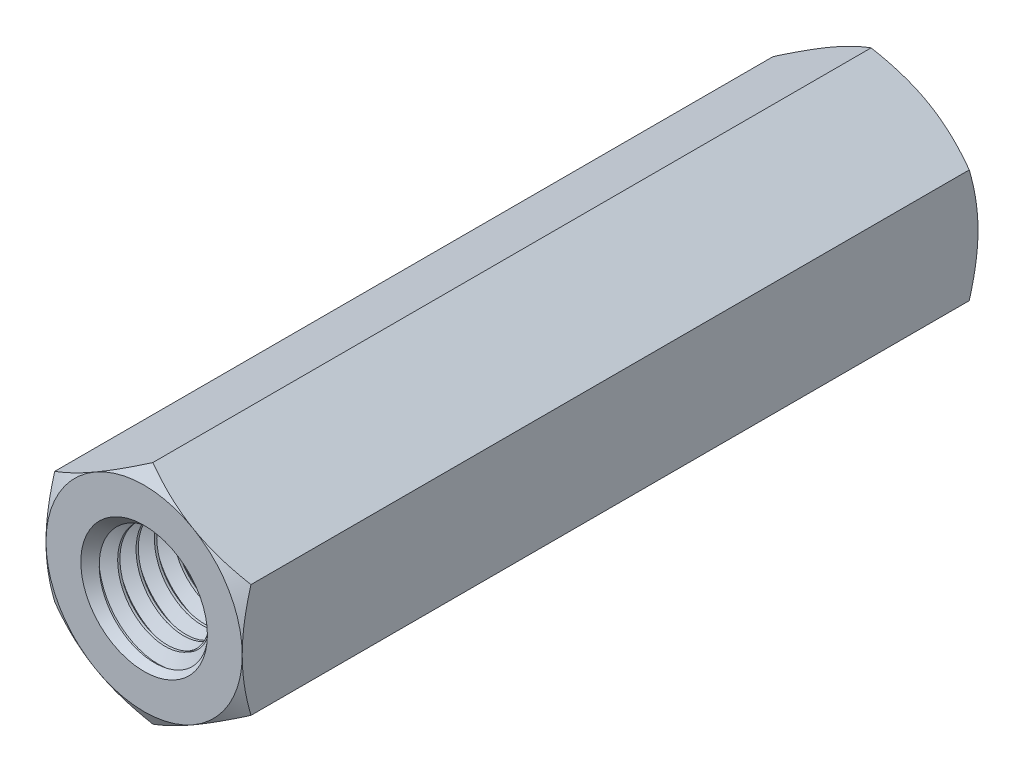
SolidWorks part; units mm, degrees
ref_plane "Front Plane" through (0, 0, 0) normal (0, 0, 1) x (1, 0, 0)
ref_plane "Top Plane" through (0, 0, 0) normal (0, 1, 0) x (1, 0, 0)
ref_plane "Right Plane" through (0, 0, 0) normal (1, 0, 0) x (0, 0, -1)
sketch "Sketch1" plane through (0, 0, 0) normal (1, 0, 0) x (0, 0, -1)
  line L0 (-30, 0) -> (30, 0) construction
  line L1 (-30, 8) -> (-30, -8) construction
  line L2 (30, 8) -> (30, -8) construction
  line L3 (0, 0) -> (0, 8) construction
  line L4 (-31.4062, 5.1624) -> (-29.9063, 5.1624) construction
  line L5 (-29.9063, 5.1624) -> (-30.6562, 3.8633) construction
  line L6 (-30.6562, 3.8633) -> (-30.6562, 4.0257) construction
  line L7 (-31.4062, 5.1624) -> (-30.6562, 3.8633) construction
  line L8 (-31.3125, 5) -> (-30, 5) construction
  line L9 (-30.75, 4.0257) -> (-30.5625, 4.0257) construction
  line L10 (-30.6562, 5) -> (-30.6562, 5.1624) construction
  line L11 (-31.3594, 5.0812) -> (-29.9531, 5.0812) construction
  point P0 (-30, 5)
  point P4 (0, 0)
  point P8 (-30, 0)
  point P11 (30, 0)
  point P12 (-30, -5)
  point P18 (-14, 0)
  point P23 (-30.6562, 5)
  point P26 (-30.6562, 4.0257)
  point P31 (-30.6562, 5.0812)
  dimension "Length" = 60
  dimension "Hex" = 16
  dimension "Thread OD" = 10
  dimension "Thread Length" = 16
  dimension "D1" = 60
  dimension "Pitch" = 1.5
  dimension "D2" = 0.1875
sketch "Sketch2" plane through (0, 0, 0) normal (0, 0, 1) x (1, 0, 0)
  line L1 (0, 9.2376) -> (-8, 4.6188)
  line L2 (-8, 4.6188) -> (-8, -4.6188)
  line L3 (-8, -4.6188) -> (0, -9.2376)
  line L4 (0, -9.2376) -> (8, -4.6188)
  line L5 (8, -4.6188) -> (8, 4.6188)
  line L6 (8, 4.6188) -> (0, 9.2376)
  circle A0 centre (0, 0) radius 8 construction
extrude "Hex Extrude" add sketch "Sketch2" along normal up to vertex (30 mm away) and the other way up to vertex (30 mm away) up to point (0, 0, 30) other way up to point (0, 0, -30)
sketch "Sketch6" plane through (0, 0, 30) normal (0, 0, 1) x (1, 0, 0)
  circle A0 centre (0, 0) radius 8
  circle A1 centre (0, 0) radius 8 construction
extrude "Hex Cut" cut sketch "Sketch6" against normal through all draft 60 flip side to cut
sketch "Sketch8" plane through (0, 0, 30) normal (0, 0, 1) x (1, 0, 0)
  circle A0 centre (0, 0) radius 5
extrude "Hex Hole Cut" cut sketch "Sketch8" against normal up to vertex (16 mm away) up to point (0, 0, 14)
sketch "Sketch9" plane through (0, 0, 14) normal (0, 0, 1) x (1, 0, 0)
  circle A1 centre (0, 0) radius 5
  circle A2 centre (0, 0) radius 5
  dimension "D1" = 0
extrude "Hex Hole Taper Cut" cut sketch "Sketch9" against normal through all draft 60
pattern_circular "Hex Cut CirPattern" count 2 over 360 about axis through (0, 0, 0) along (0, 1, 0) of "Hex Cut", "Hex Hole Cut", "Hex Hole Taper Cut"
sketch "Sketch3" plane through (0, 0, 30) normal (0, 0, 1) x (1, 0, 0)
  circle A1 centre (0, 0) radius 5
curve "Helix/Spiral1" pitch 1.5 height 17.5 radius 5 centre (0, 0, 30) axis (0, 0, -1) start towards (0, 1, 0)
sketch "Sketch4" plane through (0, 0, 0) normal (1, 0, 0) x (0, 0, -1)
  line L0 (-31.3594, 5.0812) -> (-30.75, 4.0257)
  line L1 (-30.75, 4.0257) -> (-30.5625, 4.0257)
  line L2 (-30.5625, 4.0257) -> (-29.9531, 5.0812)
  line L3 (-29.9531, 5.0812) -> (-31.3594, 5.0812)
sweep "Sweep1" add profiles "Sketch4" path "Helix/Spiral1"
pattern_circular "CirPattern1" count 2 over 360 about axis through (0, 0, 0) along (0, 1, 0) of "Sweep1"
sketch "Sketch5" plane through (0, 0, 0) normal (1, 0, 0) x (0, 0, -1)
  line L0 (-30, 0) -> (30, 0) construction
  line L1 (-30, 0) -> (30, 0) construction
  line L2 (-14, -5) -> (-14, 5) construction
  line L3 (-30, -5) -> (-30, 5) construction
  line L4 (-30, 8) -> (-30, -8) construction
  line L5 (-30, 5) -> (-31.3125, 5) construction
  line L7 (-31.4062, 3.8633) -> (-28.4519, 3.8633)
  line L9 (-30, -5) -> (-14, -5) construction
  line L10 (-22, -5) -> (-22, 5) construction
  line L16 (-31.4062, 5.1624) -> (-29.9063, 5.1624) construction
  line L17 (-31.4062, 5.1624) -> (-30, 5.1624)
  line L19 (0, 0) -> (0, 8) construction
  line L20 (0, 0) -> (0, 8) construction
  line L33 (-31.4062, 5.1624) -> (-31.4062, 3.8633)
  line L34 (-30, 5.1624) -> (-28.4519, 3.8633)
  line L35 (30, 5.1624) -> (28.4519, 3.8633)
  line L36 (31.4062, 3.8633) -> (28.4519, 3.8633)
  line L37 (31.4062, 5.1624) -> (31.4062, 3.8633)
  line L38 (31.4062, 5.1624) -> (30, 5.1624)
  point P6 (-14, 0)
  point P12 (-30, 0)
  dimension "D1" = 40
revolve "Cut-Revolve1" cut sketch "Sketch5" angle 360 about L1
equation "\"D2@Sketch1\"=\"Pitch@Sketch1\"/8"
equation "\"D3@Helix/Spiral1\"=\"Thread Length@Sketch1\" + \"Pitch@Sketch1\""
equation "\"D4@Helix/Spiral1\"=\"Pitch@Sketch1\""
